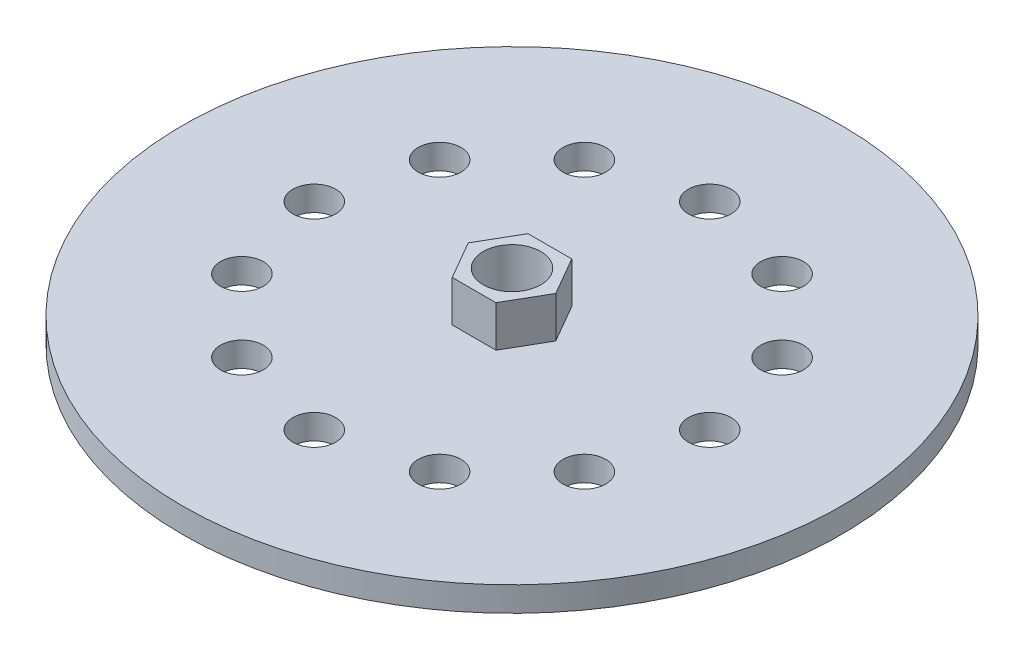
SolidWorks part; units mm, degrees
ref_plane "Front Plane" through (0, 0, 0) normal (0, 0, 1) x (1, 0, 0)
ref_plane "Top Plane" through (0, 0, 0) normal (0, 1, 0) x (1, 0, 0)
ref_plane "Right Plane" through (0, 0, 0) normal (1, 0, 0) x (0, 0, -1)
sketch "Sketch1" plane through (0, 0, 0) normal (0, 1, 0) x (1, 0, 0)
  circle A0 centre (0, 0) radius 50.8
  dimension "D1" = 101.6
extrude "Boss-Extrude1" add sketch "Sketch1" along normal blind 3.81
sketch "Sketch4" plane through (0, 3.81, 0) normal (0, 1, 0) x (1, 0, 0)
  line L0 (-3.3729, 5.842) -> (3.3729, 5.842)
  line L1 (3.3729, 5.842) -> (6.7458, 0)
  line L2 (6.7458, 0) -> (3.3729, -5.842)
  line L3 (3.3729, -5.842) -> (-3.3729, -5.842)
  line L4 (-3.3729, -5.842) -> (-6.7458, 0)
  line L5 (-6.7458, 0) -> (-3.3729, 5.842)
  circle A0 centre (0, 0) radius 4.445
  point P6 (0, 5.842)
  dimension "D3" = 8.89
  dimension "D1" = 120
  dimension "D2" = 11.684
extrude "Boss-Extrude2" add sketch "Sketch4" along normal blind 6.35 contours L5 L4 L3 L2 L1 L0 A0 region at (0, 3.81, -5.6635)
sketch "Sketch5" plane through (0, 3.81, 0) normal (0, 1, 0) x (1, 0, 0)
  circle A0 centre (0, 30.48) radius 3.302
  circle A1 centre (15.24, 26.3965) radius 3.302
  circle A2 centre (26.3965, 15.24) radius 3.302
  circle A3 centre (30.48, 0) radius 3.302
  circle A4 centre (26.3965, -15.24) radius 3.302
  circle A5 centre (15.24, -26.3965) radius 3.302
  circle A6 centre (0, -30.48) radius 3.302
  circle A7 centre (-15.24, -26.3965) radius 3.302
  circle A8 centre (-26.3965, -15.24) radius 3.302
  circle A9 centre (-30.48, 0) radius 3.302
  circle A10 centre (-26.3965, 15.24) radius 3.302
  circle A11 centre (-15.24, 26.3965) radius 3.302
  point P28 (0, 0)
  dimension "D2" = 6.604
  dimension "D1" = 30.48
extrude "Cut-Extrude1" cut sketch "Sketch5" against normal through all
